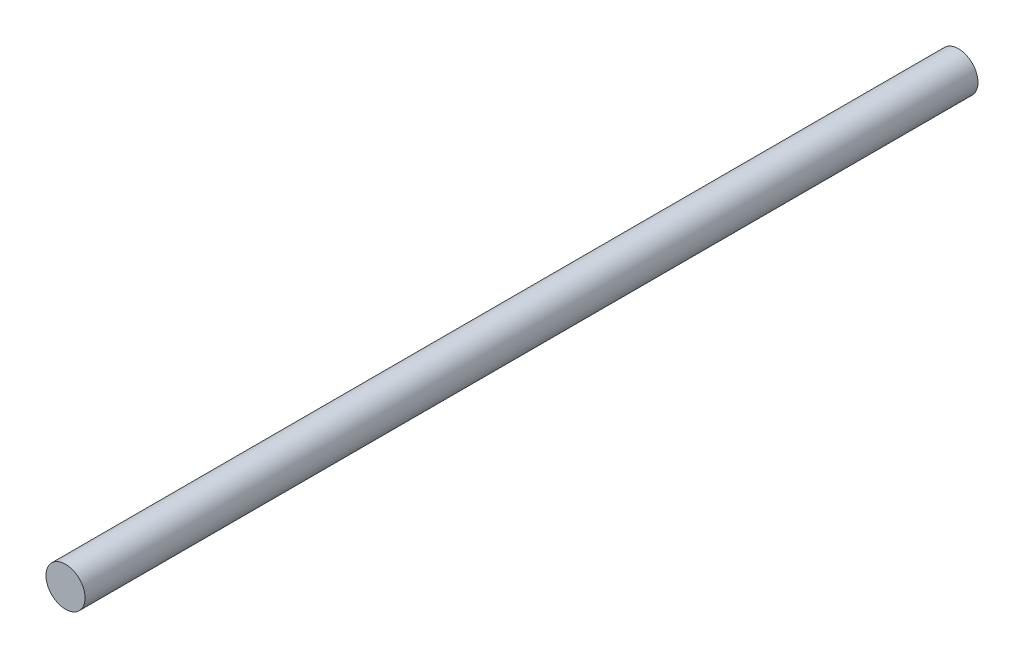
SolidWorks part; units mm, degrees
ref_plane "前视基准面" through (0, 0, 0) normal (0, 0, 1) x (1, 0, 0)
ref_plane "上视基准面" through (0, 0, 0) normal (0, 1, 0) x (1, 0, 0)
ref_plane "右视基准面" through (0, 0, 0) normal (1, 0, 0) x (0, 0, -1)
other "Configuration Table"
sketch "草图1" plane through (0, 0, 0) normal (0, 0, 1) x (1, 0, 0)
  circle A0 centre (0, 0) radius 3
  dimension "D1" = 6
extrude "凸台-拉伸1" add sketch "草图1" along normal blind 137
